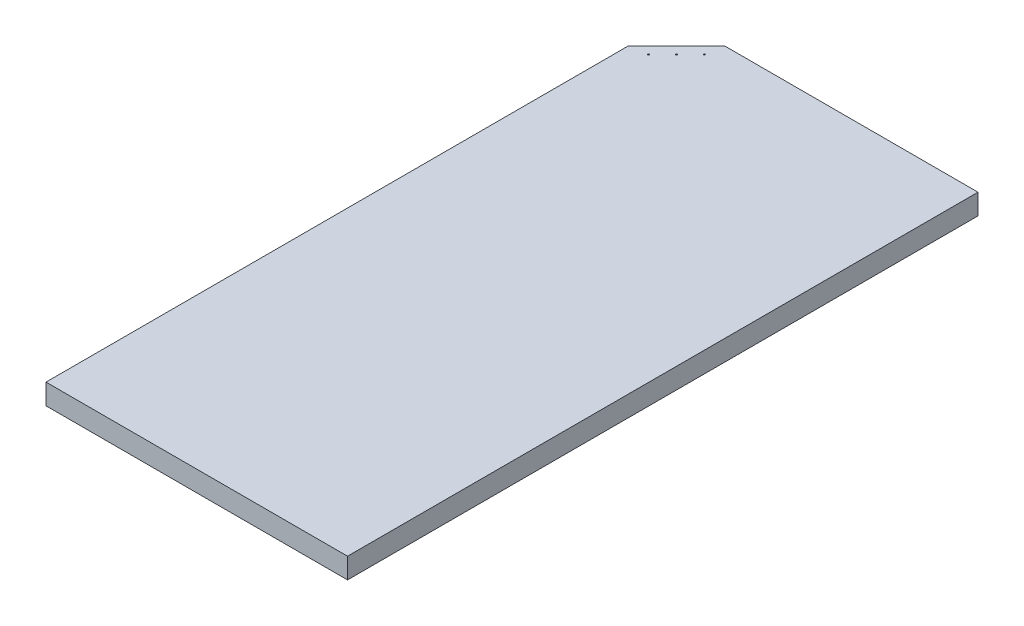
SolidWorks part; units mm, degrees
ref_plane "Front Plane" through (0, 0, 0) normal (0, 0, 1) x (1, 0, 0)
ref_plane "Top Plane" through (0, 0, 0) normal (0, 1, 0) x (1, 0, 0)
ref_plane "Right Plane" through (0, 0, 0) normal (1, 0, 0) x (0, 0, -1)
sketch "Sketch1" plane through (0, 0, 0) normal (0, 1, 0) x (1, 0, 0)
  line L1 (-139.2879, 131.2521) -> (140.1121, 131.2521)
  line L2 (-139.2879, 131.2521) -> (-139.2879, -452.9479)
  line L3 (-139.2879, -452.9479) -> (140.1121, -452.9479)
  line L4 (140.1121, 131.2521) -> (140.1121, -452.9479)
  dimension "D1" = 279.4
  dimension "D2" = 584.2
extrude "Boss-Extrude1" add sketch "Sketch1" along normal blind 19.05
sketch "Sketch2" plane through (0, 19.05, 0) normal (0, 1, 0) x (1, 0, 0)
  line L0 (-139.2879, 86.3508) -> (-94.3866, 131.2521) construction
  line L1 (-139.2879, 131.2521) -> (-139.2879, -452.9479) construction
  line L2 (140.1121, 131.2521) -> (-139.2879, 131.2521) construction
  line L3 (-94.3866, 131.2521) -> (-80.9162, 117.7817) construction
  line L4 (-80.9162, 117.7817) -> (-125.8175, 72.8804) construction
  line L5 (-125.8175, 72.8804) -> (-139.2879, 86.3508) construction
  line L6 (-123.0336, 89.1347) -> (-110.1021, 102.0662) construction
  line L7 (-116.8373, 108.8014) -> (-103.3669, 95.331) construction
  line L8 (-97.1705, 114.9978) -> (-110.1021, 102.0662) construction
  line L9 (0.4121, 1204.4021) -> (-983.8379, 220.1521) construction
  circle A0 centre (-110.1021, 102.0662) radius 0.635
  circle A1 centre (-97.1705, 114.9978) radius 0.635
  circle A2 centre (-123.0336, 89.1347) radius 0.635
  point P10 (-132.5527, 79.6156)
  point P19 (-108.8495, 100.8137)
  dimension "D4" = 1.27
  dimension "D1" = 19.05
  dimension "D2" = 63.5
  dimension "D3" = 18.288
extrude "Cut-Extrude1" cut sketch "Sketch2" against normal through all both and the other way through all
sketch "Sketch3" plane through (0, 19.05, 0) normal (0, 1, 0) x (1, 0, 0)
  line L0 (-139.2879, 86.3508) -> (-94.3866, 131.2521) construction
  line L1 (-139.2879, 86.3508) -> (-94.3866, 131.2521)
  line L2 (-94.3866, 131.2521) -> (-139.2879, 131.2521)
  line L3 (-139.2879, 131.2521) -> (-139.2879, -452.9479) construction
  line L4 (-139.2879, 131.2521) -> (-139.2879, 86.3508)
extrude "Cut-Extrude2" cut sketch "Sketch3" against normal through all
